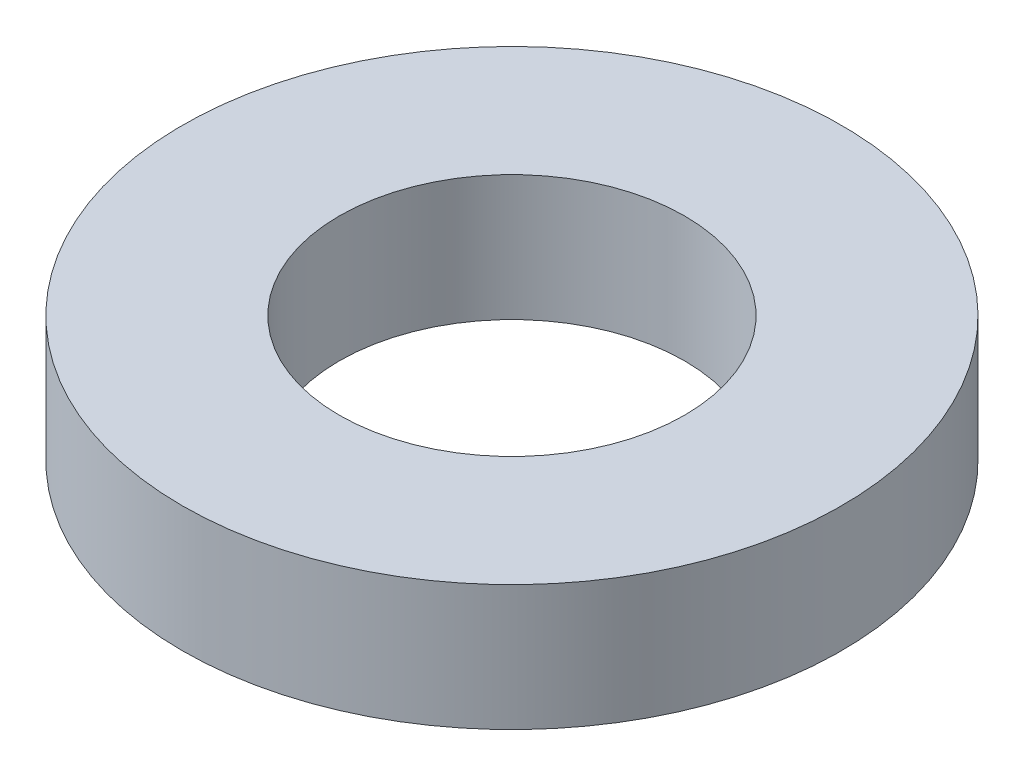
SolidWorks part; units mm, degrees
ref_plane "Front Plane" through (0, 0, 0) normal (0, 0, 1) x (1, 0, 0)
ref_plane "Top Plane" through (0, 0, 0) normal (0, 1, 0) x (1, 0, 0)
ref_plane "Right Plane" through (0, 0, 0) normal (1, 0, 0) x (0, 0, -1)
sketch "Sketch1" plane through (0, 0, 0) normal (0, 1, 0) x (1, 0, 0)
  circle A0 centre (0, 0) radius 52.5
  dimension "FLANGE_OD" = 105
extrude "Boss-Extrude1" add sketch "Sketch1" along normal blind 20
sketch "Sketch2" plane through (0, 0, 0) normal (0, 1, 0) x (1, 0, 0)
  circle A0 centre (0, 0) radius 27.5
  dimension "BORE_D" = 55
extrude "Cut-Extrude1" cut sketch "Sketch2" along normal through all
sketch "Sketch3" plane through (0, 20, 0) normal (0, 1, 0) x (1, 0, 0)
  circle A0 centre (0, 0) radius 16.6005 construction
  circle A1 centre (-16.6005, 0) radius 3.8173
  dimension "BOLT_D" = 7.6347
  dimension "BOLT_PCD" = 33.2009
extrude "Cut-Extrude2" cut sketch "Sketch3" against normal blind 12.2393 rebuild error yes
pattern_circular "CirPattern1" count 4 over 360 rebuild error yes
